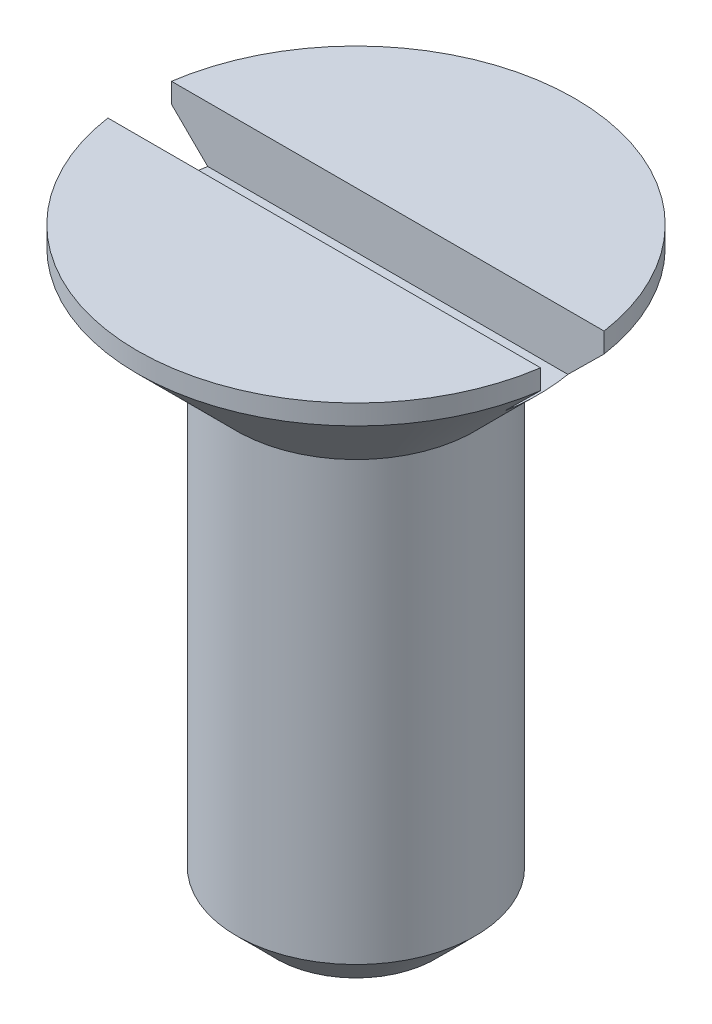
SolidWorks part; units mm, degrees
ref_plane "Спереди" through (0, 0, 0) normal (0, 0, 1) x (1, 0, 0)
ref_plane "Сверху" through (0, 0, 0) normal (0, 1, 0) x (1, 0, 0)
ref_plane "Справа" through (0, 0, 0) normal (1, 0, 0) x (0, 0, -1)
sketch "Эскиз1" plane through (0, 0, 0) normal (0, 0, 1) x (1, 0, 0)
  line L0 (0, 125.7632) -> (0, 0) construction
  line L2 (0, 92.035) -> (0, 77.035)
  line L3 (0, 92.035) -> (5.5, 92.035)
  line L4 (3, 89.035) -> (3, 77.035)
  line L5 (3, 89.035) -> (5.5, 91.535)
  line L6 (3, 77.035) -> (0, 77.035)
  line L7 (5.5, 92.035) -> (5.5, 91.535)
  dimension "D1" = 5.5
  dimension "D2" = 15
  dimension "D3" = 3
  dimension "D5" = 3
revolve "Повернуть1" add sketch "Эскиз1" angle 360 about L0
ref_axis "Ось4" through (0, 5.1336, 0) along (0, -1, 0)
sketch "Эскиз13" plane through (0, 92.035, 0) normal (0, 1, 0) x (-1, 0, 0)
  line L1 (5.5, -0.8) -> (-5.5, -0.8)
  line L2 (5.5, -0.8) -> (5.5, 0.8)
  line L3 (5.5, 0.8) -> (-5.5, 0.8)
  line L4 (-5.5, -0.8) -> (-5.5, 0.8)
  dimension "D1" = 5.5
  dimension "D2" = 11
  dimension "D3" = 0.8
  dimension "D4" = 1.6
extrude "Вырез-Вытянуть9" cut sketch "Эскиз13" against normal blind 1.4
chamfer "Фаска1" distance 1 angle 45 1 edges at (-3, 77.035, 0)
